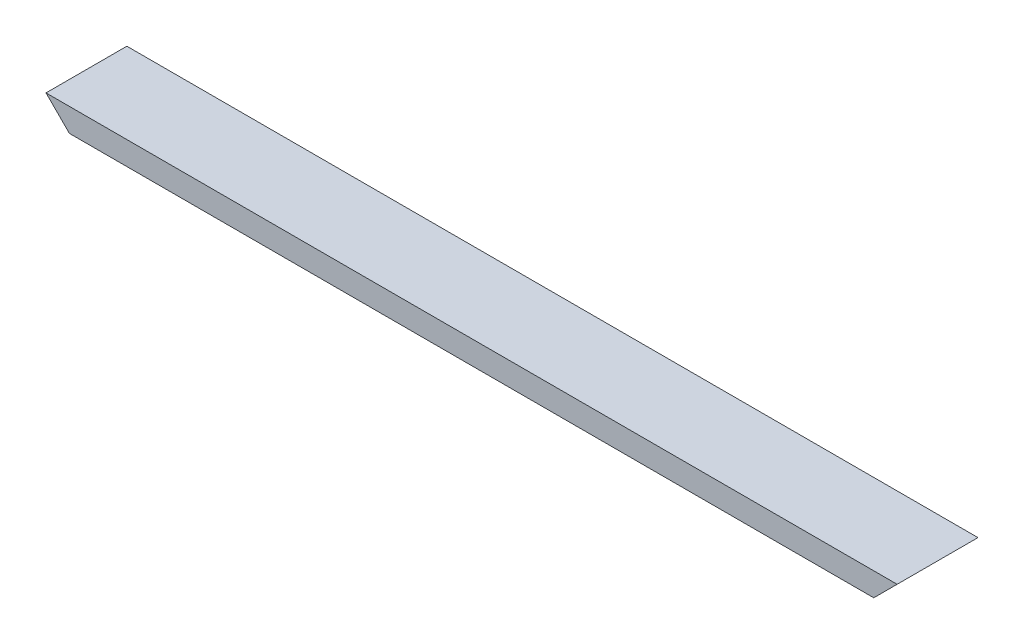
SolidWorks part; units mm, degrees
material "Stainless Steel (ferritic)"
ref_plane "Front Plane" through (0, 0, 0) normal (0, 0, 1) x (1, 0, 0)
ref_plane "Top Plane" through (0, 0, 0) normal (0, 1, 0) x (1, 0, 0)
ref_plane "Right Plane" through (0, 0, 0) normal (1, 0, 0) x (0, 0, -1)
sketch "Sketch1" plane through (0, 0, 0) normal (1, 0, 0) x (0, 0, -1)
  line L0 (-17.5, 4) -> (17.5, 4)
  line L1 (-19, -5.5) -> (19, -5.5)
  line L2 (-19, -5.5) -> (-19, 5.5)
  line L3 (-19, 5.5) -> (19, 5.5)
  line L4 (19, -5.5) -> (19, 5.5)
  line L5 (-19, -5.5) -> (19, 5.5) construction
  line L6 (-19, 5.5) -> (19, -5.5) construction
  line L7 (17.5, -4) -> (17.5, 4)
  line L8 (-17.5, -4) -> (17.5, -4)
  line L9 (-17.5, -4) -> (-17.5, 4)
  point P0 (0, 0)
  dimension "D1" = 38
  dimension "D2" = 11
  dimension "D3" = 1.5
extrude "Boss-Extrude1" add sketch "Sketch1" along normal blind 400
sketch "Sketch2" plane through (0, 0, -19) normal (0, 0, -1) x (-1, 0, 0)
  line L0 (0, 5.5) -> (-11, -5.5)
  line L1 (-400, -5.5) -> (0, -5.5) construction
  line L2 (0, -5.5) -> (0, 5.5) construction
  dimension "D1" = 45
extrude "Cut-Extrude1" cut sketch "Sketch2" against normal through all and the other way through all
sketch "Sketch3" plane through (0, 0, -19) normal (0, 0, -1) x (-1, 0, 0)
  line L0 (-400, 5.5) -> (-389, -5.5)
  line L1 (-400, -5.5) -> (-11, -5.5) construction
  line L2 (-400, -5.5) -> (-400, 5.5) construction
  dimension "D1" = 45
extrude "Cut-Extrude3" cut sketch "Sketch3" against normal through all and the other way through all flip side to cut
